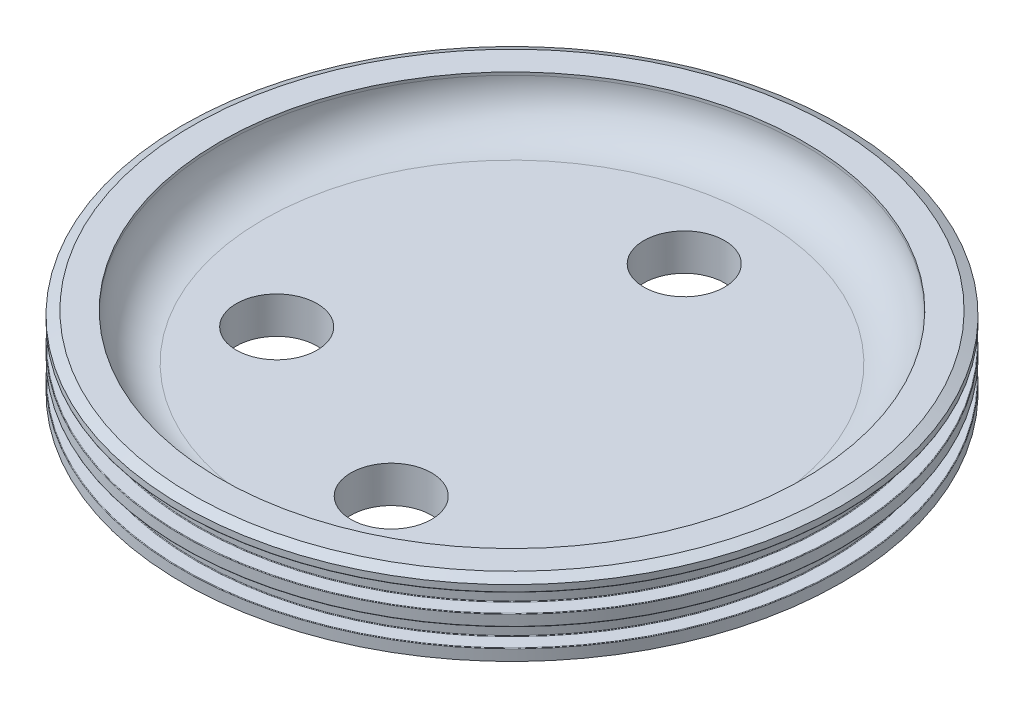
SolidWorks part; units mm, degrees
material "6061-T6 (SS)"
ref_plane "Front Plane" through (0, 0, 0) normal (0, 0, 1) x (1, 0, 0)
ref_plane "Top Plane" through (0, 0, 0) normal (0, 1, 0) x (1, 0, 0)
ref_plane "Right Plane" through (0, 0, 0) normal (1, 0, 0) x (0, 0, -1)
sketch "Sketch1" plane through (0, 0, 0) normal (0, 0, 1) x (1, 0, 0)
  line L0 (0, 48.1922) -> (0, -25.6743) construction
  line L1 (0, 0) -> (72.898, 0)
  line L2 (72.898, 0) -> (72.898, 2.54)
  line L3 (72.898, 2.54) -> (69.6468, 2.54)
  line L4 (69.6468, 2.54) -> (69.6468, 6.604)
  line L5 (69.6468, 6.604) -> (72.898, 6.604)
  line L6 (72.898, 6.604) -> (72.898, 9.144)
  line L7 (72.898, 9.144) -> (69.6468, 9.144)
  line L8 (64.5668, 15.748) -> (64.5668, 5.588)
  line L9 (64.5668, 5.588) -> (0, 5.588)
  line L10 (0, 5.588) -> (0, 0)
  line L11 (69.6468, 9.144) -> (69.6468, 13.208)
  line L12 (69.6468, 13.208) -> (72.898, 13.208)
  line L13 (72.898, 13.208) -> (72.898, 15.748)
  line L14 (72.898, 15.748) -> (64.5668, 15.748)
  dimension "D1" = 145.796
  dimension "D2" = 4.064
  dimension "D5" = 5.588
  dimension "D7" = 4.064
  dimension "D3" = 2.54
  dimension "D4" = 2.54
  dimension "D6" = 69.6468
  dimension "D8" = 5.08
revolve "Revolve1" add sketch "Sketch1" angle 360 about L0
sketch "Sketch6" plane through (0, 0, 0) normal (0, -1, 0) x (1, 0, 0)
  circle A0 centre (0, 0) radius 66.04
  dimension "D1" = 132.08
extrude "Boss-Extrude1" add sketch "Sketch6" along normal blind 2.54
fillet "CNC ID Fillet" radius 0.127 5 edges at (-69.6468, 6.604, 0) (-69.6468, 2.54, 0) (66.04, 0, 0) (-69.6468, 13.208, 0) (-69.6468, 9.144, 0)
fillet "CNC OD Fillet" radius 0.127 5 edges at (-72.898, 6.604, 0) (-72.898, 2.54, 0) (-72.898, 9.144, 0) (-72.898, 13.208, 0) (66.04, -2.54, 0)
chamfer "CNC Chamfers" distance 1.016 angle 65 1 edges at (-72.898, 15.748, 0) first distance on face at (-72.898, 13.335, 0)
hole_wizard "Pipe Tap Drill for 1/2 Tap - Fill Valve" positions "Sketch13" profile "Sketch14" hole size "1/2" standard "ANSI Inch" end condition through all
sketch "Sketch13" plane through (0, -2.54, 0) normal (0, -1, 0) x (-1, 0, 0)
  point P4 (0, 38.1)
  dimension "D1" = 38.1
sketch "Sketch14" plane through (0, -2.54, -38.1) normal (1, 0, 0) x (0, 0, -1)
  line L0 (0, 0) -> (0, 18.288)
  line L1 (0, 18.288) -> (8.9281, 18.288)
  line L2 (8.9281, 18.288) -> (8.9281, 0)
  line L5 (8.9281, 0) -> (0, 0)
  line L11 (0, -6.35) -> (0, 107.95) construction
  dimension "Thru Hole Dia." = 17.8562
  dimension "Thru Hole Depth" = 18.288
hole_wizard "Pipe Tap Drill for 1/4 Tap - Solenoid Valve" positions "Sketch15" profile "Sketch16" hole size "1/2" standard "ANSI Inch" end condition through all
sketch "Sketch15" plane through (0, -2.54, 0) normal (0, -1, 0) x (-1, 0, 0)
  line L2 (-12.0892, -38.8003) -> (0, 0) construction
  line L3 (0, 0) -> (0, -38.8003) construction
  point P4 (-12.0892, -38.8003)
  dimension "D1" = 17.306
  dimension "D2" = 40.64
  dimension "D3" = 38.8003
sketch "Sketch16" plane through (12.0892, -2.54, 38.8003) normal (1, 0, 0) x (0, 0, -1)
  line L0 (0, 0) -> (0, 18.288)
  line L1 (0, 18.288) -> (8.9281, 18.288)
  line L2 (8.9281, 18.288) -> (8.9281, 0)
  line L5 (8.9281, 0) -> (0, 0)
  line L11 (0, -6.35) -> (0, 107.95) construction
  dimension "Thru Hole Dia." = 17.8562
  dimension "Thru Hole Depth" = 18.288
hole_wizard "Pipe Tap Drill for 1/2 Tap - Cryo Valve" positions "Sketch17" profile "Sketch18" hole size "1/2" standard "ANSI Inch" end condition through all
sketch "Sketch17" plane through (0, -2.54, 0) normal (0, -1, 0) x (-1, 0, 0)
  line L0 (32.9956, -19.05) -> (17.2813, -19.05) construction
  line L2 (32.9956, -19.05) -> (0, 0) construction
  point P4 (32.9956, -19.05)
  dimension "D1" = 30
  dimension "D2" = 38.1
sketch "Sketch18" plane through (-32.9956, -2.54, 19.05) normal (1, 0, 0) x (0, 0, -1)
  line L0 (0, 0) -> (0, 18.288)
  line L1 (0, 18.288) -> (8.9281, 18.288)
  line L2 (8.9281, 18.288) -> (8.9281, 0)
  line L5 (8.9281, 0) -> (0, 0)
  line L11 (0, -6.35) -> (0, 107.95) construction
  dimension "Thru Hole Dia." = 17.8562
  dimension "Thru Hole Depth" = 18.288
fillet "Fillet1" radius 9.525 1 edges at (-64.5668, 5.588, 0)
equation "\"D6@Sketch1\"=5.484/2"
